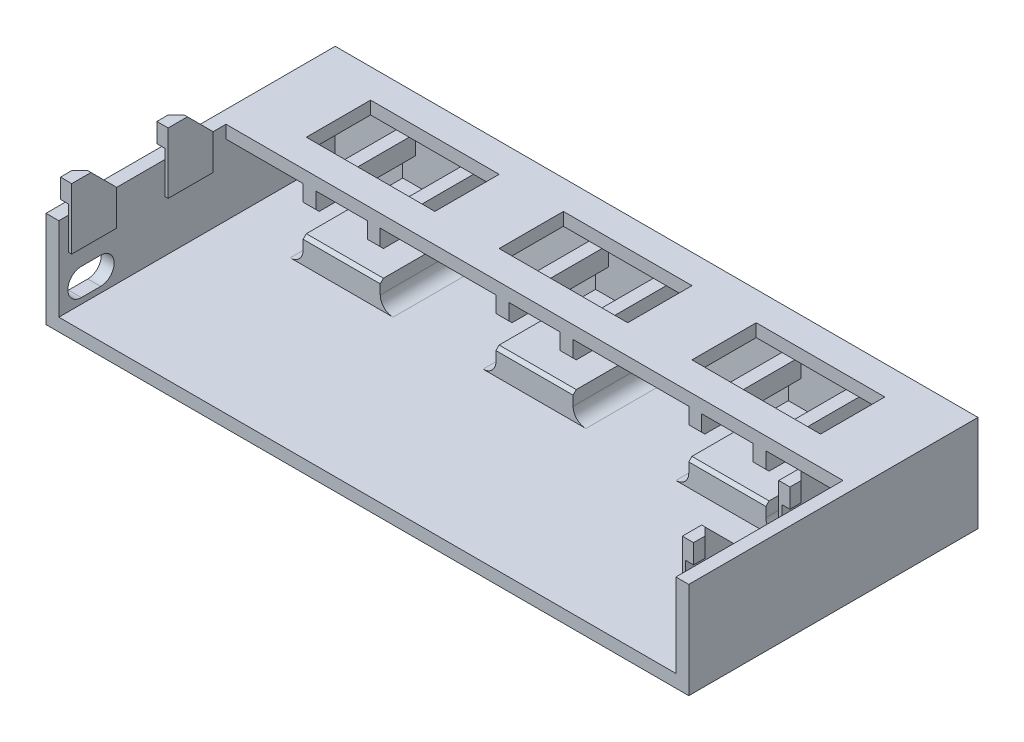
SolidWorks part; units mm, degrees
ref_plane "Front Plane" through (0, 0, 0) normal (0, 0, 1) x (1, 0, 0)
ref_plane "Top Plane" through (0, 0, 0) normal (0, 1, 0) x (1, 0, 0)
ref_plane "Right Plane" through (0, 0, 0) normal (1, 0, 0) x (0, 0, -1)
sketch "Sketch1" plane through (0, 0, 0) normal (1, 0, 0) x (0, 0, -1)
  line L1 (-22.5, -7.5) -> (22.5, -7.5)
  line L2 (-22.5, -7.5) -> (-22.5, 7.5)
  line L3 (-22.5, 7.5) -> (22.5, 7.5)
  line L4 (22.5, -7.5) -> (22.5, 7.5)
  line L5 (-22.5, -7.5) -> (22.5, 7.5) construction
  line L6 (-22.5, 7.5) -> (22.5, -7.5) construction
  point P0 (0, 0)
  dimension "D1" = 45
  dimension "D2" = 15
extrude "Boss-Extrude1" add sketch "Sketch1" along normal mid plane 100
sketch "Sketch2" plane through (0, 7.5, 0) normal (0, 1, 0) x (1, 0, 0)
  line L0 (50, -22.5) -> (-50, -22.5) construction
  line L1 (48, -22.5) -> (-48, -22.5)
  line L2 (48, -22.5) -> (48, 3.5)
  line L3 (48, 3.5) -> (-48, 3.5)
  line L4 (-48, -22.5) -> (-48, 3.5)
  line L5 (50, 22.5) -> (-50, 22.5) construction
  line L6 (50, 22.5) -> (50, -22.5) construction
  line L7 (-50, 22.5) -> (-50, -22.5) construction
  dimension "D1" = 19
  dimension "D2" = 2
  dimension "D3" = 2
extrude "Cut-Extrude1" cut sketch "Sketch2" against normal offset from surface (13 mm away) 2 up to face at (0, -7.5, 0)
shell "Shell1" thickness 2 removed face at (0, 1, -3.5)
sketch "Sketch3" plane through (0, 7.5, 0) normal (0, 1, 0) x (1, 0, 0)
  line L0 (-48, 3.5) -> (-48, 22.5) construction
  line L1 (-10, 18) -> (10, 18)
  line L2 (-10, 18) -> (-10, 8)
  line L3 (-10, 8) -> (10, 8)
  line L4 (10, 18) -> (10, 8)
  line L5 (50, 22.5) -> (-50, 22.5) construction
  line L6 (-48, 22.5) -> (-48, 13) construction
  line L7 (-48, 13) -> (50, 13) construction
  line L8 (50, 22.5) -> (50, -22.5) construction
  line L10 (0, 0) -> (0, 38.1624) construction
  point P10 (-10, 13)
  point P17 (0, 8)
  dimension "D1" = 20
  dimension "D2" = 10
extrude "Cut-Extrude2" cut sketch "Sketch3" against normal up to surface (2 mm away) up to face at (0, 5.5, -12)
pattern_linear "LPattern1" count 2 spacing 30 along (-1, 0, 0) count 2 spacing 30 along (1, 0, 0) of "Cut-Extrude2"
sketch "Sketch4" plane through (0, 0, -20.5) normal (0, 0, 1) x (1, 0, 0)
  line L0 (48, -5.5) -> (-48, -5.5) construction
  line L1 (-36, -5.5) -> (-24, -5.5)
  line L2 (-36, -5.5) -> (-36, -1.5)
  line L3 (-36, -1.5) -> (-24, -1.5)
  line L4 (-24, -5.5) -> (-24, -1.5)
  line L5 (48, 5.5) -> (-48, 5.5) construction
  line L6 (-36, 5.5) -> (-34, 5.5)
  line L7 (-36, 5.5) -> (-36, 2.5)
  line L8 (-36, 2.5) -> (-34, 2.5)
  line L9 (-34, 5.5) -> (-34, 2.5)
  line L10 (-30, 5.5) -> (-30, -5.5) construction
  line L11 (-24, 5.5) -> (-26, 5.5)
  line L12 (-24, 5.5) -> (-24, 2.5)
  line L13 (-24, 2.5) -> (-26, 2.5)
  line L14 (-26, 5.5) -> (-26, 2.5)
  line L15 (-30, -5.5) -> (-30, 5.5) construction
  line L16 (-30, 5.5) -> (-20, 5.5) construction
  line L17 (-20, 5.5) -> (-20, 7.5) construction
  line L18 (-30, 5.5) -> (-40, 5.5) construction
  line L19 (-40, 5.5) -> (-40, 7.5) construction
  point P24 (0, 0)
  point P25 (-30, -1.5)
  point P26 (0, 0)
  dimension "D1" = 4
  dimension "D2" = 4
  dimension "D3" = 12
  dimension "D4" = 8
extrude "Boss-Extrude2" add sketch "Sketch4" along normal up to surface (17 mm away) up to face at (0, 6.5, -3.5)
sketch "Sketch5" plane through (0, -1.5, 0) normal (0, 1, 0) x (1, 0, 0)
  line L1 (-24, 7) -> (-36, 7) construction
  line L2 (-24, 7) -> (-24, 19) construction
  line L3 (-24, 19) -> (-36, 19)
  line L4 (-36, 7) -> (-36, 19) construction
  line L5 (-24, 7) -> (-36, 19) construction
  line L6 (-24, 19) -> (-36, 7) construction
  line L7 (-40, 18) -> (-20, 8) construction
  line L8 (-36, 19) -> (-36, 20.5)
  line L9 (-36, 20.5) -> (-24, 20.5)
  line L10 (-24, 20.5) -> (-24, 19)
  line L11 (-36, 3.5) -> (-36, 20.5) construction
  point P0 (-30, 13)
  point P10 (-36, 20.5)
  dimension "D1" = 12
  dimension "D2" = 12
extrude "Boss-Extrude3" add sketch "Sketch5" along normal up to surface (7 mm away) up to face at (30, 5.5, -13)
chamfer "Chamfer1" distance 0.5 angle 45 3 edges at (-35, 2.5, -3.5) (-25, 2.5, -3.5) (-30, -1.5, -3.5)
fillet "Fillet1" radius 2 2 edges at (-36, -5.5, -12) (-24, -5.5, -12)
pattern_linear "LPattern2" count 3 spacing 30 along (1, 0, 0) of "Fillet1", "Boss-Extrude2", "Chamfer1", "Boss-Extrude3"
sketch "Sketch6" plane through (48, 0, 0) normal (-1, 0, 0) x (0, 0, 1)
  line L0 (22.5, 7.5) -> (-3.5, 7.5) construction
  line L1 (18, 12) -> (21, 12)
  line L2 (18, 12) -> (18, 9)
  line L3 (18, 9) -> (21, 9)
  line L4 (21, 12) -> (21, 9)
  line L5 (18, 12) -> (21, 9) construction
  line L6 (18, 9) -> (21, 12) construction
  line L8 (22.5, -5.5) -> (22.5, 7.5) construction
  line L10 (3, 9) -> (6, 9)
  line L11 (3, 9) -> (3, 12)
  line L12 (3, 12) -> (6, 12)
  line L13 (6, 9) -> (6, 12)
  line L14 (3, 9) -> (6, 12) construction
  line L15 (3, 12) -> (6, 9) construction
  point P0 (19.5, 10.5)
  point P9 (4.5, 10.5)
  dimension "D1" = 1.5
  dimension "D2" = 1.5
  dimension "D3" = 3
  dimension "D4" = 3
  dimension "D5" = 15
extrude "Boss-Extrude4" add sketch "Sketch6" against normal blind 1.25 separate body
sketch "Sketch7" plane through (48, 0, 0) normal (-1, 0, 0) x (0, 0, 1)
  line L0 (18, 12) -> (13.5, 7.5)
  line L1 (22.5, 7.5) -> (-3.5, 7.5) construction
  line L2 (13.5, 7.5) -> (21, 7.5)
  line L3 (21, 7.5) -> (21, 12)
  line L4 (21, 12) -> (18, 12)
  line L5 (3, 12) -> (-1.5, 7.5)
  line L6 (-1.5, 7.5) -> (6, 7.5)
  line L7 (6, 7.5) -> (6, 12)
  line L8 (6, 12) -> (3, 12)
  line L9 (6, 9) -> (6, 12) construction
  dimension "D1" = 45
  dimension "D2" = 45
extrude "Boss-Extrude5" add sketch "Sketch7" along normal blind 0.5
sketch "Sketch8" plane through (47.5, 0, 0) normal (-1, 0, 0) x (0, 0, 1)
  line L0 (22.5, 7.5) -> (-3.5, 7.5) construction
  line L1 (6, 7.5) -> (-1.5, 7.5)
  line L2 (6, 7.5) -> (6, 2.5)
  line L3 (6, 2.5) -> (-1.5, 2.5)
  line L4 (-1.5, 7.5) -> (-1.5, 2.5)
  line L5 (21, 7.5) -> (13.5, 7.5)
  line L6 (21, 7.5) -> (21, 2.5)
  line L7 (21, 2.5) -> (13.5, 2.5)
  line L8 (13.5, 7.5) -> (13.5, 2.5)
  point P9 (0, 0)
  point P10 (16.5, 7.5)
  point P13 (-2.2321, 7.5)
  dimension "D1" = 5
extrude "Boss-Extrude6" add sketch "Sketch8" against normal up to surface (0.5 mm away) up to face at (48, 2.5, -0.5)
chamfer "Chamfer2" distance 0.5 angle 45 2 edges at (47.5, 5, -1.5) (47.5, 5, 13.5)
chamfer "Chamfer4" distance 1.25 angle 45 2 edges at (49.25, 10.5, 3) (49.25, 10.5, 18)
mirror "Mirror7" about plane through (0, 0, 0) normal (1, 0, 0) of "Chamfer4", "Chamfer2", "Boss-Extrude6", "Boss-Extrude4", "Boss-Extrude5"
sketch "Sketch10" plane through (-50, 0, 0) normal (-1, 0, 0) x (0, 0, 1)
  line L0 (19, -2.5) -> (16, -2.5) construction
  line L1 (19, -4.6) -> (16, -4.6)
  line L2 (19, -0.4) -> (16, -0.4)
  line L3 (22.5, -7.5) -> (-22.5, -7.5) construction
  line L4 (22.5, 7.5) -> (22.5, -7.5) construction
  arc A0 (19, -4.6) -> (19, -0.4) centre (19, -2.5) ccw
  arc A1 (16, -0.4) -> (16, -4.6) centre (16, -2.5) ccw
  point P2 (17.5, -2.5)
  point P7 (21.1, -2.5)
  point P8 (13.9, -2.5)
  point P9 (17.197, -3.5974)
  dimension "D1" = 7.2
  dimension "D2" = 4.2
  dimension "D3" = 5
  dimension "D4" = 5
extrude "Cut-Extrude3" cut sketch "Sketch10" against normal up to surface (2 mm away) up to face at (-48, 3.9286, 5.3571)
